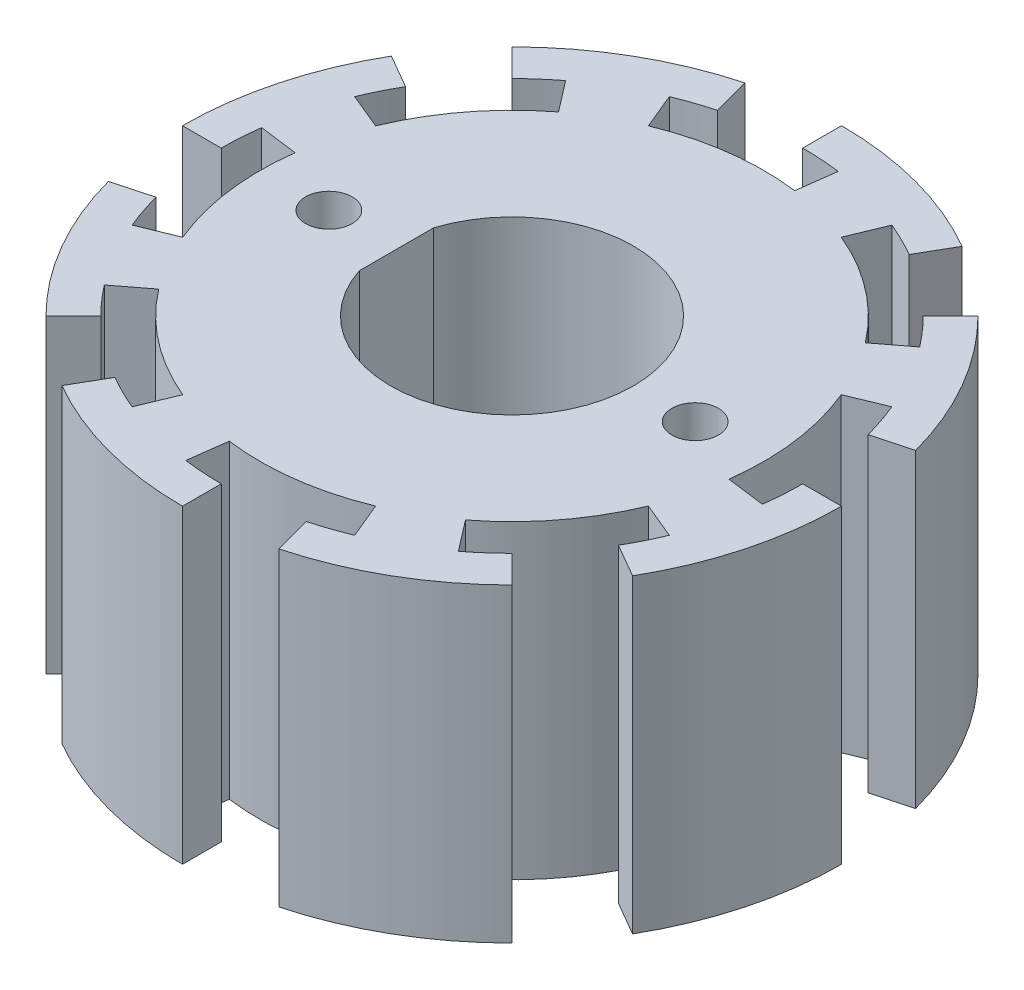
SolidWorks part; units mm, degrees
material "ABS"
ref_plane "Front Plane" through (0, 0, 0) normal (1, 0, 0) x (0, 1, 0)
ref_plane "Top Plane" through (0, 0, 0) normal (0, 0, 1) x (0, 1, 0)
ref_plane "Right Plane" through (0, 0, 0) normal (0, 1, 0) x (-1, 0, 0)
sketch "Sketch1" plane through (0, 0, 0) normal (1, 0, 0) x (0, 1, 0)
  line L0 (0, 0) -> (-37.386, 0) construction
  line L1 (0, 7.9502) -> (-20.32, 7.9502)
  line L2 (-20.32, 7.9502) -> (-20.32, 21.59)
  line L3 (-20.32, 21.59) -> (0, 21.59)
  line L4 (0, 21.59) -> (0, 18.415)
  line L5 (0, 18.415) -> (-5.08, 18.415)
  line L6 (-5.08, 18.415) -> (-5.08, 14.3002)
  line L7 (-5.08, 14.3002) -> (0, 14.3002)
  line L8 (0, 14.3002) -> (0, 7.9502)
  line L9 (0, 18.415) -> (0, 14.3002)
  line L10 (0, 18.415) -> (0, 14.3002)
  dimension "D1" = 7.9502
  dimension "D2" = 6.35
  dimension "D3" = 21.59
  dimension "D4" = 20.32
  dimension "D5" = 3.175
  dimension "D6" = 5.08
revolve "Revolve1" add sketch "Sketch1" angle 360 about L0 region at (0, -10.7816, 14.6406) region at (0, -2.54, 16.3576)
sketch "Sketch2" plane through (0, 0, 0) normal (0, 1, 0) x (-1, 0, 0)
  line L0 (0, 0) -> (0, 21.59) construction
  line L1 (0, 0) -> (-5.5879, 20.8543) construction
  line L2 (0, 0) -> (-10.795, 18.6975) construction
  line L3 (0, 0) -> (5.5879, 20.8543) construction
  line L4 (-5.5879, 20.8543) -> (-4.9305, 18.4009)
  line L5 (0, 0) -> (-7.2901, 17.5999) construction
  line L6 (0, 0) -> (2.4865, 18.887) construction
  line L7 (0, 21.59) -> (0, 19.05)
  line L8 (-7.2901, 17.5999) -> (-6.3181, 15.2533)
  line L9 (2.4865, 18.887) -> (2.155, 16.3688)
  circle A0 centre (0, 0) radius 21.59 construction
  circle A1 centre (0, 0) radius 19.05 construction
  circle A2 centre (0, 0) radius 21.59 construction
  circle A3 centre (0, 0) radius 16.51 construction
  arc A4 (-4.9305, 18.4009) -> (-7.2901, 17.5999) centre (0, 0) ccw
  arc A5 (0, 19.05) -> (2.4865, 18.887) centre (0, 0) cw
  arc A6 (-6.3181, 15.2533) -> (2.155, 16.3688) centre (0, 0) cw
  arc A7 (-5.5879, 20.8543) -> (0, 21.59) centre (0, 0) cw
  dimension "D6" = 43.18
  dimension "D7" = 38.1
  dimension "D8" = 33.02
  dimension "D1" = 15
  dimension "D2" = 15
  dimension "D3" = 15
  dimension "D4" = 7.5
  dimension "D5" = 7.5
extrude "Cut-Extrude1" cut sketch "Sketch2" against normal through all
sketch "Sketch4" plane through (0, 0, 0) normal (0, 0, 1) x (0, 1, 0)
  line L0 (0, 0) -> (-8.21, 0) construction
  line L1 (-20.32, 0) -> (0, 0) construction
pattern_circular "CirPattern1" count 8 every 45 about axis through (0, 0, 0) along (0, -1, 0) of "Cut-Extrude1"
sketch "Sketch5" plane through (0, 0, 0) normal (0, 1, 0) x (1, 0, 0)
  line L0 (-7.5692, -2.4316) -> (-7.5692, 2.4316)
  circle A0 centre (0, 0) radius 7.9502 construction
  arc A1 (-7.5692, 2.4316) -> (-7.5692, -2.4316) centre (0, 0) cw
  arc A2 (-7.5692, 2.4316) -> (-7.5692, -2.4316) centre (0, 0) ccw
  dimension "D1" = 7.5692
extrude "Boss-Extrude1" add sketch "Sketch5" against normal up to surface (20.32 mm away) contours L0 A2 region at (-7.7219, 0, 0) up to face at (0, -20.32, 0)
sketch "Sketch6" plane through (0, 0, 0) normal (0, 1, 0) x (-1, 0, 0)
  circle A0 centre (0, 0) radius 6.9342
  circle A1 centre (0, 0) radius 12.2
  dimension "D1" = 13.8684
  dimension "D2" = 24.4
extrude "40 tooth gear" [suppressed] add sketch "Sketch6" along normal blind 6.5
sketch "Sketch7" [suppressed] plane through (0, 6.5, 0) normal (0, 1, 0) x (-1, 0, 0)
  circle A0 centre (0, 0) radius 6.9342
  circle A1 centre (0, 0) radius 13.2
  circle A2 centre (0, 0) radius 6.9342 construction
  dimension "D1" = 26.4
extrude "Boss-Extrude3" [suppressed] add sketch "Sketch7" along normal blind 1.016
sketch "Sketch8" plane through (0, 0, 0) normal (0, 1, 0) x (-1, 0, 0)
  line L0 (12, 0) -> (-12, 0) construction
  circle A0 centre (-12, 0) radius 1.524
  circle A1 centre (12, 0) radius 1.524
  point P5 (0, 0)
  dimension "D1" = 3.048
  dimension "D2" = 24
sketch "Sketch11" plane through (0, -20.32, 0) normal (0, 1, 0) x (-1, 0, 0)
  circle A0 centre (-12, 0) radius 2.921
  circle A1 centre (12, 0) radius 2.921
  dimension "D1" = 5.842
extrude "Cut-Extrude2" cut sketch "Sketch8" against normal through all
extrude "Cut-Extrude3" cut sketch "Sketch11" along normal blind 12.7
equation "\"D1@Sketch5\"=0.313-0.015"
equation "\"D1@40 tooth gear\" = 6.5mm"
equation "\"D2@Sketch6\"=24.4mm"
equation "\"D1@Sketch7\"=26.4mm"
equation "\"D1@Sketch6\"=2*(0.313-0.04)"
